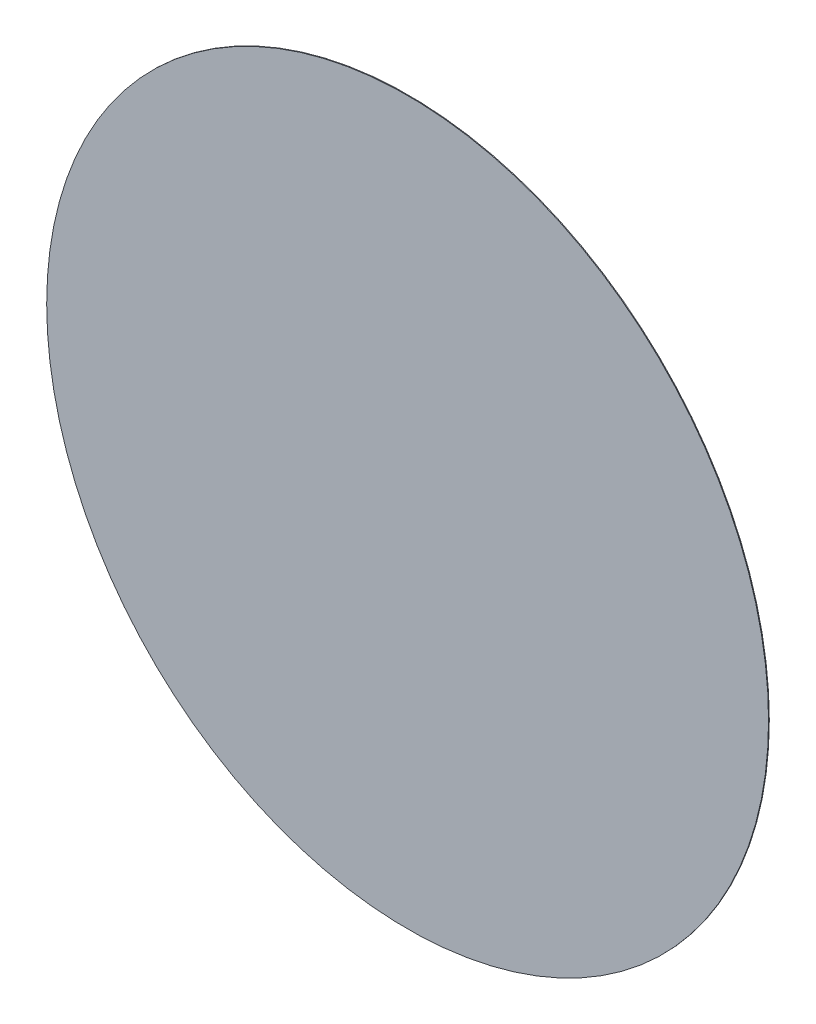
SolidWorks part; units mm, degrees
material "6061-T4 (SS)"
ref_plane "Front Plane" through (0, 0, 0) normal (0, 0, 1) x (1, 0, 0)
ref_plane "Top Plane" through (0, 0, 0) normal (0, 1, 0) x (1, 0, 0)
ref_plane "Right Plane" through (0, 0, 0) normal (1, 0, 0) x (0, 0, -1)
sketch "Sketch1" plane through (0, 0, 0) normal (0, 0, 1) x (1, 0, 0)
  circle A0 centre (0, 0) radius 4.75
  dimension "D1" = 9.5
extrude "Boss-Extrude1" add sketch "Sketch1" along normal blind 0.01
sketch "Sketch4" plane through (0, 0, 0) normal (0, 0, -1) x (-1, 0, 0)
  point P0 (0, 0)
